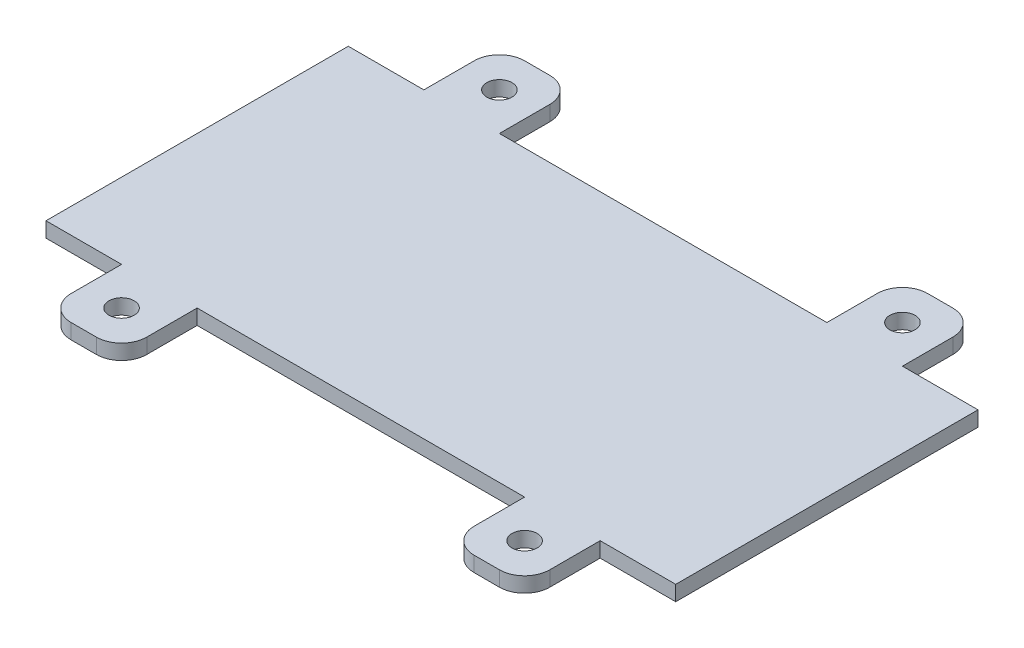
SolidWorks part; units mm, degrees
material "Сталь 3 ГОСТ 535-88"
ref_plane "Спереди" through (0, 0, 0) normal (0, 0, 1) x (1, 0, 0)
ref_plane "Сверху" through (0, 0, 0) normal (0, 1, 0) x (1, 0, 0)
ref_plane "Справа" through (0, 0, 0) normal (1, 0, 0) x (0, 0, -1)
sketch "Эскиз1" plane through (0, 0, 0) normal (0, 1, 0) x (1, 0, 0)
  line L1 (-125, 60) -> (125, 60)
  line L2 (-125, 60) -> (-125, -60)
  line L3 (-125, -60) -> (125, -60)
  line L4 (125, 60) -> (125, -60)
  line L5 (0, -60) -> (0, 60) construction
  line L6 (-125, 0) -> (125, 0) construction
  point P0 (0, 0)
  dimension "D1" = 120
  dimension "D2" = 250
extrude "Бобышка-Вытянуть1" add sketch "Эскиз1" along normal blind 6
sketch "Эскиз2" plane through (0, 0, 0) normal (0, 1, 0) x (1, 0, 0)
  line L0 (125, 60) -> (-125, 60) construction
  line L1 (-95, 60) -> (-65, 60)
  line L2 (-95, 60) -> (-95, 90)
  line L3 (-95, 90) -> (-65, 90)
  line L4 (-65, 60) -> (-65, 90)
  line L5 (-125, 60) -> (-125, -60) construction
  line L6 (-80, 90) -> (-80, 60) construction
  circle A0 centre (-80, 75) radius 5
  dimension "D4" = 10
  dimension "D1" = 30
  dimension "D2" = 30
  dimension "D3" = 30
extrude "Бобышка-Вытянуть2" add sketch "Эскиз2" along normal up to surface (6 mm away) separate body up to face at (0, 6, 0)
fillet "Скругление1" radius 10 2 edges at (-95, 3, -90) (-65, 3, -90)
mirror "Зеркальное отражение1" about plane through (0, 0, 0) normal (1, 0, 0) of bodies 112
mirror "Зеркальное отражение3" about plane through (0, 0, 0) normal (0, 0, 1) of bodies 112 113
combine bodies "Соединить1" operation type add bodies to combine 107 114 113 112 115
